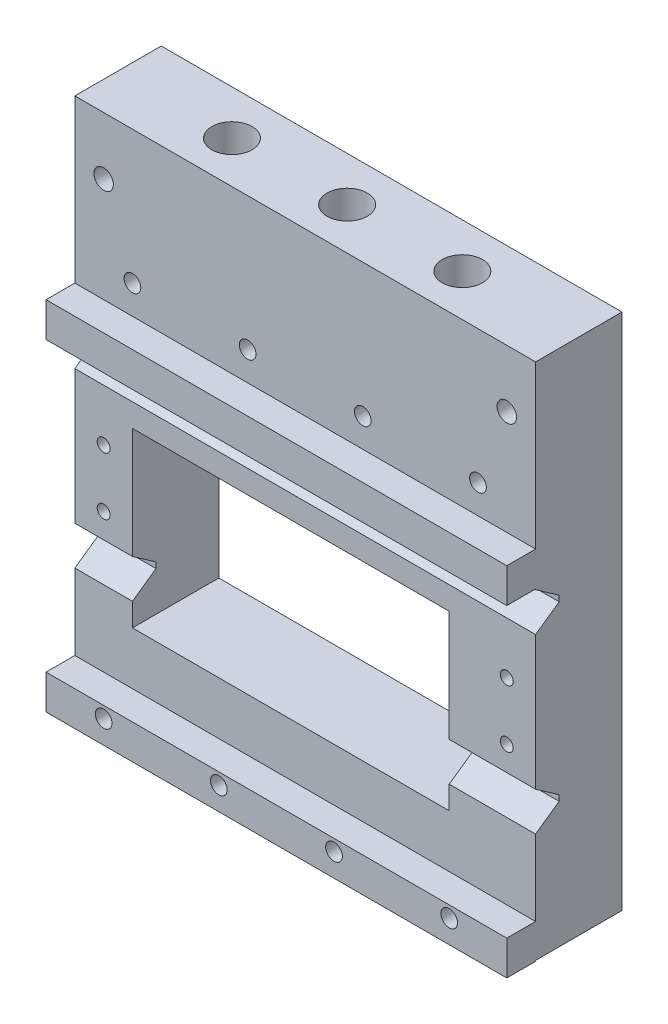
SolidWorks part; units mm, degrees
material "ABS"
ref_plane "Front Plane" through (0, 0, 0) normal (0, 0, 1) x (1, 0, 0)
ref_plane "Top Plane" through (0, 0, 0) normal (0, 1, 0) x (1, 0, 0)
ref_plane "Right Plane" through (0, 0, 0) normal (1, 0, 0) x (0, 0, -1)
sketch "Sketch1" plane through (0, 0, 0) normal (0, 0, 1) x (1, 0, 0)
  line L1 (-83.1034, 136.2931) -> (76.8966, 136.2931)
  line L2 (-83.1034, 136.2931) -> (-83.1034, -43.7069)
  line L3 (-83.1034, -43.7069) -> (76.8966, -43.7069)
  line L4 (76.8966, 136.2931) -> (76.8966, -43.7069)
  line L5 (-63.1034, 46.2931) -> (46.8966, 46.2931)
  line L6 (-63.1034, 46.2931) -> (-63.1034, -13.7069)
  line L7 (-63.1034, -13.7069) -> (46.8966, -13.7069)
  line L8 (46.8966, 46.2931) -> (46.8966, -13.7069)
  dimension "D1" = 60
  dimension "D2" = 180
  dimension "D3" = 90
  dimension "D4" = 160
  dimension "D5" = 30
  dimension "D6" = 110
extrude "Boss-Extrude1" add sketch "Sketch1" along normal blind 30
sketch "Sketch2" plane through (-83.1034, 0, 0) normal (-1, 0, 0) x (0, 0, 1)
  line L0 (30, 7.7646) -> (21.8085, 2.0289)
  line L1 (30, 136.2931) -> (30, -43.7069) construction
  line L2 (21.8085, 2.0289) -> (21.8085, 0.0289)
  line L3 (21.8085, 0.0289) -> (30, -5.7069)
  line L4 (30, -5.7069) -> (30, 7.7646)
  point P4 (30, -32.4307)
  point P7 (22.4696, -25.254)
  dimension "D1" = 10
  dimension "D2" = 10
  dimension "D3" = 2
  dimension "D4" = 38
  dimension "D5" = 125
extrude "Cut-Extrude1" cut sketch "Sketch2" against normal blind 300
sketch "Sketch11" plane through (0, 0, 30) normal (0, 0, 1) x (1, 0, 0)
  line L0 (-83.1034, 136.2931) -> (-83.1034, 7.7646) construction
  line L1 (-83.1034, -32.0013) -> (76.8966, -32.0013)
  line L2 (-83.1034, -32.0013) -> (-83.1034, -44.0013)
  line L3 (-83.1034, -44.0013) -> (76.8966, -44.0013)
  line L4 (76.8966, -32.0013) -> (76.8966, -44.0013)
  line L5 (76.8966, 7.7646) -> (76.8966, 136.2931) construction
  dimension "D1" = 12
extrude "Boss-Extrude2" add sketch "Sketch11" along normal blind 10
sketch "Sketch3" plane through (0, 136.2931, 0) normal (0, 1, 0) x (1, 0, 0)
  line L0 (-83.1034, -30) -> (-83.1034, 0) construction
  circle A0 centre (-43.1034, -15.4362) radius 3
  dimension "D1" = 40
extrude "Cut-Extrude2" cut sketch "Sketch3" against normal blind 100
sketch "Sketch4" plane through (0, 136.2931, 0) normal (0, 1, 0) x (1, 0, 0)
  circle A0 centre (-43.1034, -15.4362) radius 7
  circle A1 centre (-43.1034, -15.4362) radius 3 construction
extrude "Cut-Extrude3" cut sketch "Sketch4" against normal blind 70
pattern_linear "LPattern1" count 3 spacing 40 along (1, 0, 0) of "Cut-Extrude2", "Cut-Extrude3"
sketch "Sketch5" plane through (0, 0, 0) normal (0, 0, -1) x (-1, 0, 0)
  line L0 (83.1034, 136.2931) -> (83.1034, -43.7069) construction
  line L1 (63.1034, -13.7069) -> (-46.8966, -13.7069) construction
  circle A0 centre (73.1034, 16.2931) radius 2.2387
  dimension "D1" = 10
  dimension "D2" = 30
extrude "Cut-Extrude4" cut sketch "Sketch5" against normal blind 100
sketch "Sketch6" plane through (0, 0, 0) normal (0, 0, -1) x (-1, 0, 0)
  circle A0 centre (73.1034, 16.2931) radius 4.369
extrude "Cut-Extrude5" cut sketch "Sketch6" against normal blind 25
pattern_linear "LPattern2" count 2 spacing 20 along (0, 1, 0) count 2 spacing 140 along (1, 0, 0) of "Cut-Extrude4", "Cut-Extrude5"
sketch "Sketch9" plane through (0, 0, 0) normal (0, 0, -1) x (-1, 0, 0)
  line L0 (-76.8966, -43.7069) -> (-76.8966, 136.2931) construction
  line L1 (-76.8966, 136.2931) -> (83.1034, 136.2931) construction
  circle A0 centre (-66.8966, 116.2931) radius 3.3818
  dimension "D1" = 10
  dimension "D2" = 20
extrude "Cut-Extrude8" cut sketch "Sketch9" against normal blind 100
sketch "Sketch10" plane through (0, 0, 30) normal (0, 0, 1) x (1, 0, 0)
  circle A0 centre (66.8966, 116.2931) radius 6.9825
  circle A1 centre (66.8966, 116.2931) radius 3.3818 construction
extrude "Cut-Extrude9" cut sketch "Sketch10" against normal blind 20 from offset 10 offset against normal yes
pattern_linear "LPattern4" count 2 spacing 140 along (-1, 0, 0) of "Cut-Extrude9", "Cut-Extrude8"
pattern_linear "LPattern5" count 2 spacing 112 along (0, 1, 0) of "Boss-Extrude2"
pattern_linear "LPattern6" count 2 spacing 60 along (0, 1, 0) of "Cut-Extrude1"
sketch "Sketch7" plane through (0, 0, 0) normal (0, 0, -1) x (-1, 0, 0)
  line L2 (49.7345, 95.9987) -> (56.4724, 95.9987) construction
  circle A0 centre (63.1034, 89.9987) radius 2.9002
  dimension "D1" = 6
  dimension "D2" = 20
extrude "Cut-Extrude6" cut sketch "Sketch7" against normal blind 40
sketch "Sketch8" plane through (0, 0, 0) normal (0, 0, -1) x (-1, 0, 0)
  circle A0 centre (63.1034, 89.9987) radius 5.871
extrude "Cut-Extrude7" cut sketch "Sketch8" against normal blind 25
pattern_linear "LPattern3" count 4 spacing 40 along (1, 0, 0) count 2 spacing 126 along (0, -1, 0) of "Cut-Extrude6", "Cut-Extrude7"
